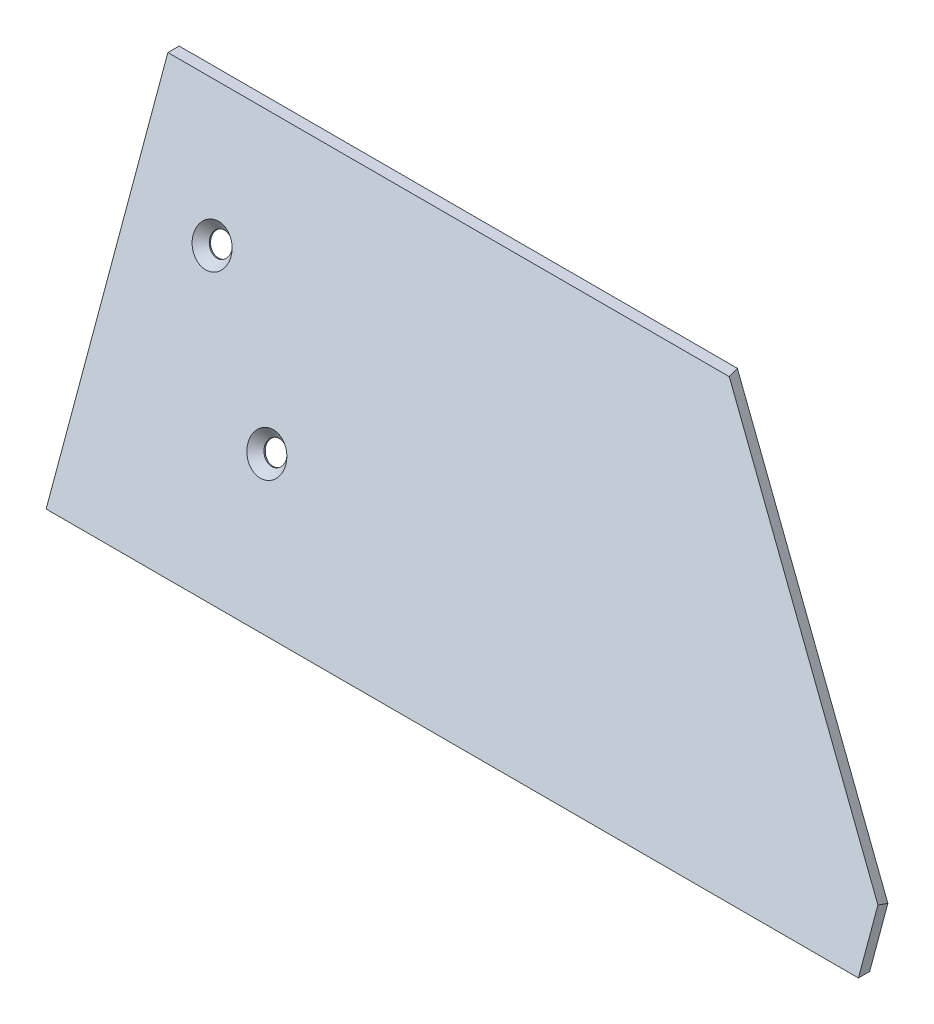
SolidWorks part; units mm, degrees
ref_plane "Front Plane" through (0, 0, 0) normal (0, 0, 1) x (1, 0, 0)
ref_plane "Top Plane" through (0, 0, 0) normal (0, 1, 0) x (1, 0, 0)
ref_plane "Right Plane" through (0, 0, 0) normal (1, 0, 0) x (0, 0, -1)
sketch "Sketch1" plane through (0, 0, 0) normal (1, 0, 0) x (0, 0, -1)
  line L0 (0, 0) -> (-2.3622, 0)
  line L1 (-2.3622, 0) -> (23.1157, 70)
  line L2 (23.1157, 70) -> (25.4779, 70)
  line L3 (25.4779, 70) -> (0, 0)
  dimension "D1" = 2.3622
  dimension "D2" = 2.3622
  dimension "D3" = 70
  dimension "D4" = 70
extrude "Main" add sketch "Sketch1" along normal mid plane 170
hole_wizard "BackBracketHoles" positions "Sketch2" profile "Sketch3" countersink size "#8" standard "ANSI Inch"
sketch "Sketch2" plane through (0, 0.7592, 2.0859) normal (0, 0.342, 0.9397) x (1, 0, 0)
  line L0 (-85, 73.6845) -> (-85, -0.8079) construction
  line L1 (85, -0.8079) -> (-85, -0.8079) construction
  point P0 (-67.6378, 50.0021)
  point P2 (-47.6378, 25.0021)
  dimension "D1" = 17.3622
  dimension "D2" = 50.81
  dimension "D3" = 25.81
  dimension "D4" = 37.3622
sketch "Sketch3" plane through (-67.6378, 47.7458, -15.0158) normal (1, 0, 0) x (0, -0.9397, 0.342)
  line L0 (0, 0) -> (0, 5)
  line L1 (0, 5) -> (2.286, 5)
  line L2 (2.286, 5) -> (2.286, 1.9285)
  line L3 (2.286, 1.9285) -> (3.9624, 0)
  line L5 (3.9624, 0) -> (0, 0)
  line L6 (-2.286, 1.9285) -> (-3.9624, 0) construction
  line L10 (0, 5) -> (-2.286, 5) construction
  line L11 (0, -6.35) -> (0, 107.95) construction
  dimension "Hole Dia." = 4.572
  dimension "Hole Depth" = 5
  dimension "Near C'Sink Dia." = 7.9248
  dimension "Near C'Sink Angle" = 82
  dimension "Drill Angle" = 180
sketch "Sketch4" plane through (0, 0.7592, 2.0859) normal (0, 0.342, 0.9397) x (1, 0, 0)
  line L4 (85, -0.8079) -> (95, -0.8079)
  line L5 (95, -0.8079) -> (31.8155, 74.4924)
  line L7 (85, 74.4924) -> (-85, 74.4924) construction
  line L9 (31.8155, 74.4924) -> (31.8155, -0.8079)
  line L10 (85, -0.8079) -> (-85, -0.8079) construction
  line L11 (31.8155, -0.8079) -> (95, -0.8079)
  line L12 (85, -0.8079) -> (85, 11.1096)
  line L13 (85, 73.6845) -> (85, -0.8079) construction
  line L14 (31.8155, 74.4924) -> (95, 74.4924)
  line L15 (95, 74.4924) -> (95, -0.8079)
  line M8 (85, -0.8079) -> (85, 73.6845)
  line M9 (85, 73.6845) -> (-85, 73.6845)
  dimension "D1" = 10
  dimension "D2" = 50
extrude "Front Cut" cut sketch "Sketch4" against normal up to next contours L5 M8 M9 | L15 L14 L5 M9 M8 region at (88.3124, 39.9714, -12.1862) region at (67.4978, 50.3996, -15.9818)
